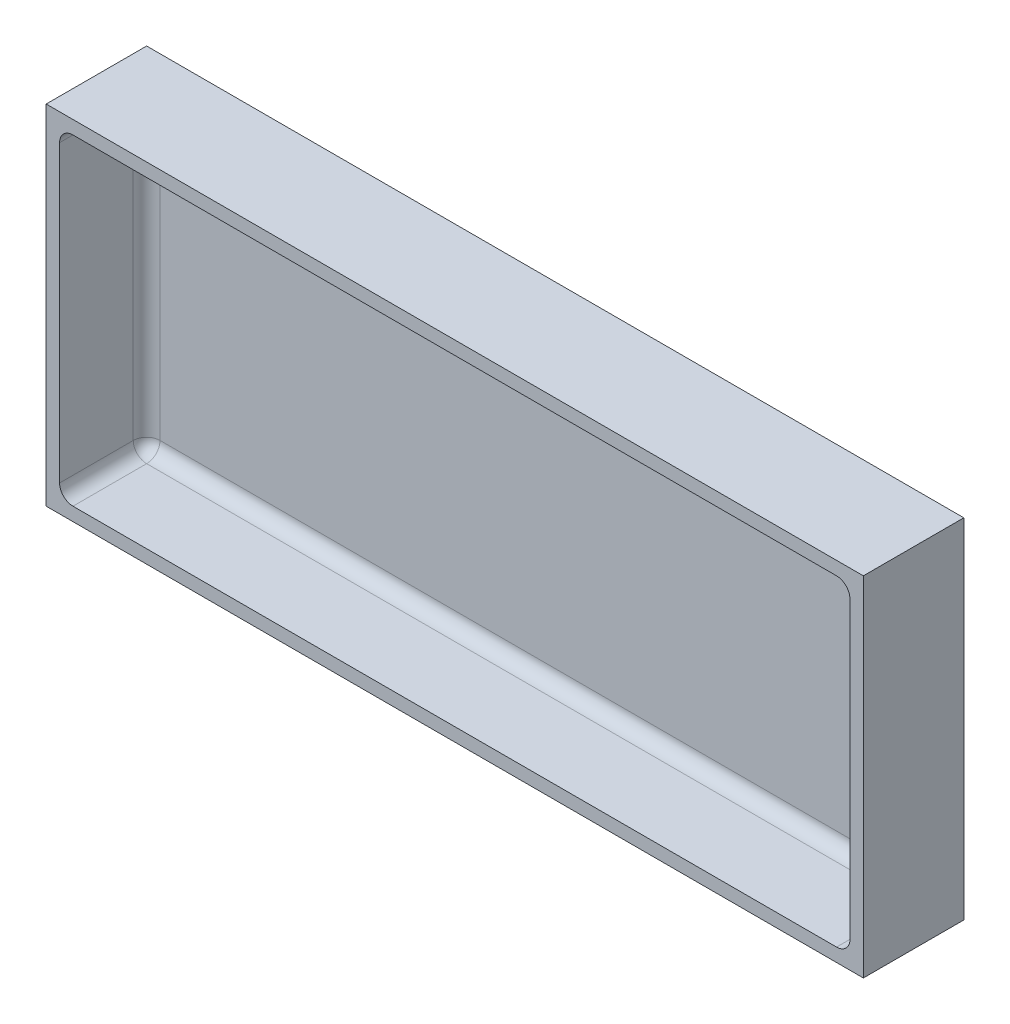
SolidWorks part; units mm, degrees
material "Alumina"
ref_plane "Front Plane" through (0, 0, 0) normal (0, 0, 1) x (1, 0, 0)
ref_plane "Top Plane" through (0, 0, 0) normal (0, 1, 0) x (1, 0, 0)
ref_plane "Right Plane" through (0, 0, 0) normal (1, 0, 0) x (0, 0, -1)
sketch "Sketch1" plane through (0, 0, 0) normal (0, 0, 1) x (1, 0, 0)
  line L1 (-61, -26) -> (61, -26)
  line L2 (-61, -26) -> (-61, 26)
  line L3 (-61, 26) -> (61, 26)
  line L4 (61, -26) -> (61, 26)
  line L5 (-61, -26) -> (61, 26) construction
  line L6 (-61, 26) -> (61, -26) construction
  point P0 (0, 0)
  dimension "D1" = 122
  dimension "D2" = 52
extrude "Boss-Extrude1" add sketch "Sketch1" against normal blind 15
shell "Shell1" thickness 2 removed face at (0, 0, 0)
fillet "Fillet1" radius 2 8 edges at (-59, 24, -6.5) (-59, -24, -6.5) (0, -24, -13) (-59, 0, -13) (0, 24, -13) (59, 0, -13) (59, 24, -6.5) (59, -24, -6.5)
